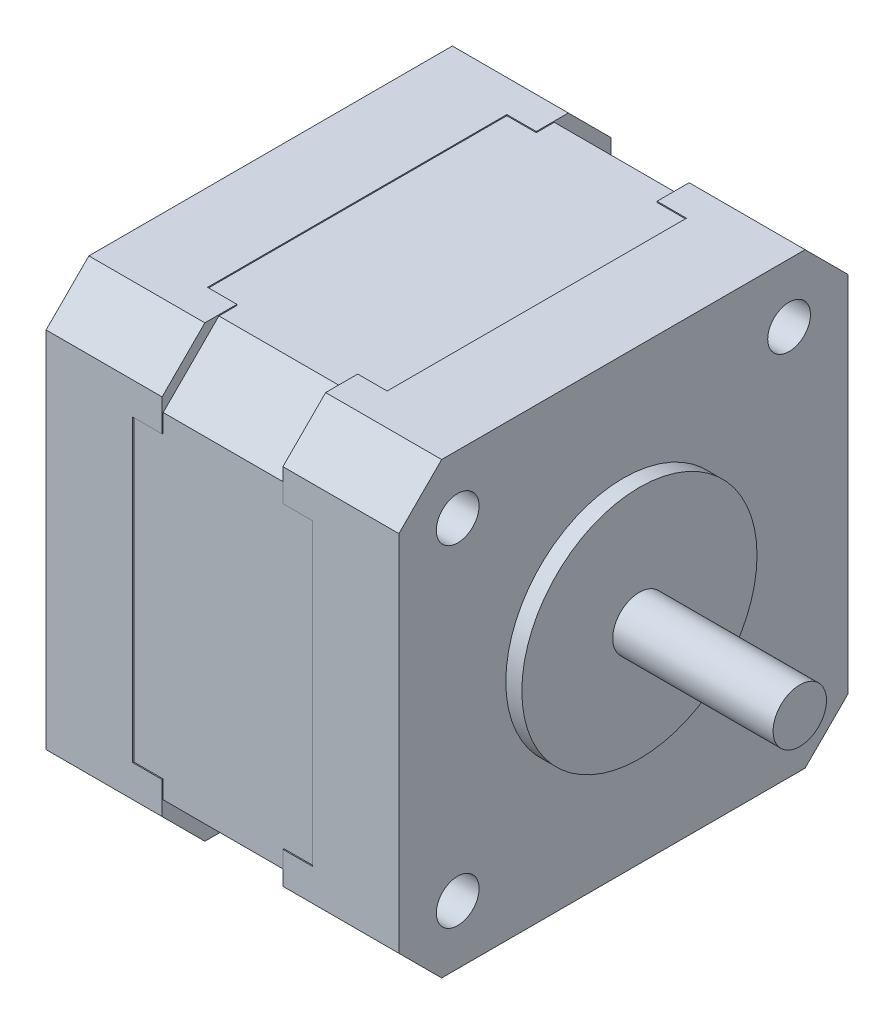
SolidWorks part; units mm, degrees
ref_plane "Alzado" through (0, 0, 0) normal (0, 0, 1) x (1, 0, 0)
ref_plane "Planta" through (0, 0, 0) normal (0, 1, 0) x (1, 0, 0)
ref_plane "Vista lateral" through (0, 0, 0) normal (1, 0, 0) x (0, 0, -1)
ref_plane "Plano1" through (-5.65, 0, 0) normal (-1, 0, 0) x (0, -1, 0)
sketch "Croquis1" plane through (-5.65, 0, 0) normal (-1, 0, 0) x (0, -1, 0)
  line L0 (20.9, -20.9) -> (20.9, 20.9)
  line L1 (20.9, 20.9) -> (-20.9, 20.9)
  line L2 (-20.9, 20.9) -> (-20.9, -20.9)
  line L3 (-20.9, -20.9) -> (20.9, -20.9)
extrude "Saliente-Extruir1" add sketch "Croquis1" against normal blind 11.3
sketch "Croquis2" plane through (5.65, 0, 0) normal (1, 0, 0) x (0, 0, -1)
  line L0 (21, 20.9) -> (21, -21)
  line L1 (21, -21) -> (-21, -21)
  line L2 (-21, -21) -> (-21, 20.9)
  line L3 (-21, 20.9) -> (21, 20.9)
extrude "Saliente-Extruir2" add sketch "Croquis2" along normal blind 10.85
sketch "Croquis3" plane through (0, 20.9, 0) normal (0, 1, 0) x (-1, 0, 0)
  line L0 (-5.65, -21) -> (-16.5, -21)
  line L1 (-16.5, -21) -> (-16.5, 21)
  line L2 (-16.5, 21) -> (-5.65, 21)
  line L3 (-5.65, 21) -> (-5.65, -21)
extrude "Saliente-Extruir3" add sketch "Croquis3" along normal blind 0.1
ref_plane "Plano2" through (-5.65, 0, 0) normal (1, 0, 0) x (0, 0, -1)
sketch "Croquis4" plane through (-5.65, 0, 0) normal (1, 0, 0) x (0, 0, -1)
  line L0 (21, 21) -> (-21, 21)
  line L1 (-21, 21) -> (-21, -21)
  line L2 (-21, -21) -> (21, -21)
  line L3 (21, -21) -> (21, 21)
extrude "Saliente-Extruir4" add sketch "Croquis4" against normal blind 10.85
ref_plane "Plano3" through (8.4, 0, 0) normal (1, 0, 0) x (0, 0, -1)
sketch "Croquis5" plane through (8.4, 0, 0) normal (1, 0, 0) x (0, 0, -1)
  line L0 (20.9, 14) -> (20.9, -14)
  line L1 (20.9, -14) -> (21, -14)
  line L2 (21, -14) -> (21, 14)
  line L3 (21, 14) -> (20.9, 14)
extrude "Cortar-Extruir1" cut sketch "Croquis5" against normal up to next
ref_plane "Plano4" through (-8.4, 0, 0) normal (-1, 0, 0) x (0, -1, 0)
sketch "Croquis6" plane through (-8.4, 0, 0) normal (-1, 0, 0) x (0, -1, 0)
  line L0 (-14, 21) -> (-14, 20.9)
  line L1 (-14, 20.9) -> (14, 20.9)
  line L2 (14, 20.9) -> (14, 21)
  line L3 (14, 21) -> (-14, 21)
extrude "Cortar-Extruir2" cut sketch "Croquis6" against normal up to next
sketch "Croquis7" plane through (0, -21, 0) normal (0, -1, 0) x (1, 0, 0)
  line L0 (8.4, -14) -> (8.4, 14)
  line L1 (8.4, 14) -> (5.65, 14)
  line L2 (5.65, 14) -> (5.65, -14)
  line L3 (5.65, -14) -> (8.4, -14)
extrude "Cortar-Extruir3" cut sketch "Croquis7" against normal blind 0.1
sketch "Croquis8" plane through (0, 0, 21) normal (0, 0, 1) x (1, 0, 0)
  line L0 (8.4, -14) -> (8.4, 14)
  line L1 (8.4, 14) -> (5.65, 14)
  line L2 (5.65, 14) -> (5.65, -14)
  line L3 (5.65, -14) -> (8.4, -14)
extrude "Cortar-Extruir4" cut sketch "Croquis8" against normal blind 0.1
sketch "Croquis9" plane through (5.65, 0, 0) normal (-1, 0, 0) x (0, 0, 1)
  line L0 (-14, 20.9) -> (14, 20.9)
  line L1 (14, 20.9) -> (14, 21)
  line L2 (14, 21) -> (-14, 21)
  line L3 (-14, 21) -> (-14, 20.9)
extrude "Cortar-Extruir5" cut sketch "Croquis9" against normal blind 2.75
sketch "Croquis10" plane through (0, -21, 0) normal (0, -1, 0) x (1, 0, 0)
  line L0 (-5.65, -14) -> (-5.65, 14)
  line L1 (-5.65, 14) -> (-8.4, 14)
  line L2 (-8.4, 14) -> (-8.4, -14)
  line L3 (-8.4, -14) -> (-5.65, -14)
extrude "Cortar-Extruir6" cut sketch "Croquis10" against normal blind 0.1
sketch "Croquis11" plane through (0, 0, -21) normal (0, 0, -1) x (-1, 0, 0)
  line L0 (5.65, 14) -> (5.65, -14)
  line L1 (5.65, -14) -> (8.4, -14)
  line L2 (8.4, -14) -> (8.4, 14)
  line L3 (8.4, 14) -> (5.65, 14)
extrude "Cortar-Extruir7" cut sketch "Croquis11" against normal blind 0.1
sketch "Croquis12" plane through (0, 21, 0) normal (0, 1, 0) x (-1, 0, 0)
  line L0 (5.65, 14) -> (5.65, -14)
  line L1 (5.65, -14) -> (8.4, -14)
  line L2 (8.4, -14) -> (8.4, 14)
  line L3 (8.4, 14) -> (5.65, 14)
extrude "Cortar-Extruir8" cut sketch "Croquis12" against normal blind 0.1
sketch "Croquis15" plane through (0, 0, 0) normal (0, 0, 1) x (1, 0, 0)
  line L0 (15.5, 11) -> (15.5, 0)
  line L1 (15.5, 0) -> (33, 0)
  line L2 (33, 0) -> (33, 2.5)
  line L3 (33, 2.5) -> (18, 2.5)
  line L4 (18, 2.5) -> (18, 11)
  line L5 (18, 11) -> (15.5, 11)
  line L6 (15.5, 0) -> (33, 0) construction
  dimension "D1" = 15
revolve "Revolución1" add sketch "Croquis15" angle 360 about L6 reverse direction yes
chamfer "Chaflán1" distance 5.2142 angle 45 4 edges at (0, -20.9, -20.9) (0, -20.9, 20.9)
chamfer "Chaflán2" distance 4 angle 45 8 edges at (-11.075, 21, -21) (-11.075, -21, 21) (11.075, -21, -21) (11.075, 21, -21) (-11.075, 21, 21) (11.075, 21, 21) (-11.075, -21, -21) (11.075, -21, 21)
ref_plane "Plano5" through (12.45, 0, 0) normal (1, 0, 0) x (0, 0, -1)
sketch "Croquis18" plane through (12.45, 0, 0) normal (1, 0, 0) x (0, 0, -1)
  line L0 (0, 0) -> (0, 2.3727) construction
  line L1 (0, 36.4567) -> (0, 0) construction
  line L2 (0, 0) -> (37.7341, 0) construction
  line L4 (15.5, -15.5) -> (-15.5, -15.5) construction
  line L5 (15.5, -15.5) -> (15.5, 15.5) construction
  line L6 (15.5, 15.5) -> (-15.5, 15.5) construction
  line L7 (-15.5, -15.5) -> (-15.5, 15.5) construction
  line L8 (15.5, -15.5) -> (-15.5, 15.5) construction
  line L9 (15.5, 15.5) -> (-15.5, -15.5) construction
  circle A0 centre (-15.5, 15.5) radius 2
  circle A1 centre (15.5, 15.5) radius 2
  circle A2 centre (15.5, -15.5) radius 2
  circle A3 centre (-15.5, -15.5) radius 2
  dimension "D3" = 4
  dimension "D1" = 15.5
  dimension "D2" = 15.5
extrude "Cortar-Extruir10" cut sketch "Croquis18" against normal blind 3 and the other way blind 6
